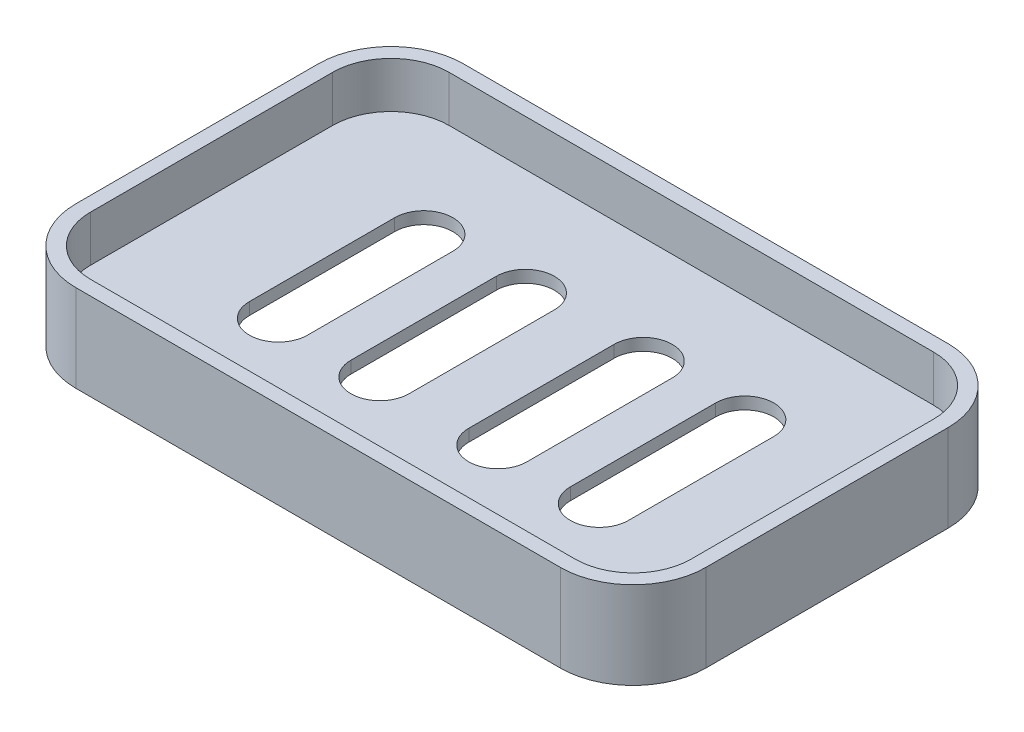
SolidWorks part; units mm, degrees
ref_plane "Front Plane" through (0, 0, 0) normal (0, 0, 1) x (1, 0, 0)
ref_plane "Top Plane" through (0, 0, 0) normal (0, 1, 0) x (1, 0, 0)
ref_plane "Right Plane" through (0, 0, 0) normal (1, 0, 0) x (0, 0, -1)
sketch "Sketch1" plane through (0, 0, 0) normal (0, 1, 0) x (1, 0, 0)
  line L0 (-98.4477, -5.2516) -> (82.5147, -5.2516) construction
  line L1 (-62.044, 34.7484) -> (37.956, 34.7484)
  line L2 (-77.044, 19.7484) -> (-77.044, -30.2516)
  line L3 (-62.044, -45.2516) -> (37.956, -45.2516)
  line L4 (52.956, 19.7484) -> (52.956, -30.2516)
  line L5 (-12.044, 47.0592) -> (-12.044, -63.0461) construction
  line L6 (-24.2076, 9.6639) -> (-24.2076, -20.3361) construction
  line L7 (-18.2076, 9.6639) -> (-18.2076, -20.3361)
  line L8 (-30.2076, 9.6639) -> (-30.2076, -20.3361)
  line L9 (-45.1595, 9.6639) -> (-45.1595, -20.3361) construction
  line L10 (-39.1595, 9.6639) -> (-39.1595, -20.3361)
  line L11 (-51.1595, 9.6639) -> (-51.1595, -20.3361)
  line L12 (21.0714, 9.6639) -> (21.0714, -20.3361) construction
  line L13 (15.0714, 9.6639) -> (15.0714, -20.3361)
  line L14 (27.0714, 9.6639) -> (27.0714, -20.3361)
  line L15 (0.1196, 9.6639) -> (0.1196, -20.3361) construction
  line L16 (-5.8804, 9.6639) -> (-5.8804, -20.3361)
  line L17 (6.1196, 9.6639) -> (6.1196, -20.3361)
  line L18 (-62.044, 31.7484) -> (37.956, 31.7484)
  line L19 (49.956, 19.7484) -> (49.956, -30.2516)
  line L20 (-62.044, -42.2516) -> (37.956, -42.2516)
  line L21 (-74.044, 19.7484) -> (-74.044, -30.2516)
  arc A0 (-77.044, 19.7484) -> (-62.044, 34.7484) centre (-62.044, 19.7484) cw
  arc A1 (52.956, 19.7484) -> (37.956, 34.7484) centre (37.956, 19.7484) ccw
  arc A2 (37.956, -45.2516) -> (52.956, -30.2516) centre (37.956, -30.2516) ccw
  arc A3 (-77.044, -30.2516) -> (-62.044, -45.2516) centre (-62.044, -30.2516) ccw
  arc A4 (-18.2076, 9.6639) -> (-30.2076, 9.6639) centre (-24.2076, 9.6639) ccw
  arc A5 (-30.2076, -20.3361) -> (-18.2076, -20.3361) centre (-24.2076, -20.3361) ccw
  arc A6 (-39.1595, 9.6639) -> (-51.1595, 9.6639) centre (-45.1595, 9.6639) ccw
  arc A7 (-51.1595, -20.3361) -> (-39.1595, -20.3361) centre (-45.1595, -20.3361) ccw
  arc A8 (15.0714, 9.6639) -> (27.0714, 9.6639) centre (21.0714, 9.6639) cw
  arc A9 (27.0714, -20.3361) -> (15.0714, -20.3361) centre (21.0714, -20.3361) cw
  arc A10 (-5.8804, 9.6639) -> (6.1196, 9.6639) centre (0.1196, 9.6639) cw
  arc A11 (6.1196, -20.3361) -> (-5.8804, -20.3361) centre (0.1196, -20.3361) cw
  arc A12 (49.956, 19.7484) -> (37.956, 31.7484) centre (37.956, 19.7484) ccw
  arc A13 (37.956, -42.2516) -> (49.956, -30.2516) centre (37.956, -30.2516) ccw
  arc A14 (-74.044, -30.2516) -> (-62.044, -42.2516) centre (-62.044, -30.2516) ccw
  arc A15 (-74.044, 19.7484) -> (-62.044, 31.7484) centre (-62.044, 19.7484) cw
  point P6 (-77.044, 34.7484)
  point P9 (52.956, 34.7484)
  point P12 (52.956, -45.2516)
  point P21 (-24.2076, -5.3361)
  point P28 (-45.1595, -5.3361)
  point P35 (21.0714, -5.3361)
  point P42 (0.1196, -5.3361)
  dimension "D3" = 15
  dimension "D4" = 15
  dimension "D5" = 15
  dimension "D7" = 6
  dimension "D8" = 6
  dimension "D1" = 130
  dimension "D2" = 80
  dimension "D6" = 15
  dimension "D9" = 3
extrude "Boss-Extrude1" add sketch "Sketch1" along normal blind 12 and the other way blind 6 contours L2 A3 L3 A2 L4 A1 L1 A0 L21 A15 L18 A12 L19 A13 L20 A14 region at (-12.044, 0, -33.222)
extrude "Boss-Extrude2" add sketch "Sketch1<3>" along normal blind 2.5 contours A15 L21 A14 L20 A13 L19 A12 L18 A7 L11 A6 L10 A5 L8 A4 L7 L14 A9 L13 A8 L17 A11 L16 A10 region at (-12.044, 0, 5.2292)
sketch "Sketch1<3>" plane through (0, 0, 0) normal (0, 1, 0) x (1, 0, 0) same geometry as "Sketch1"
